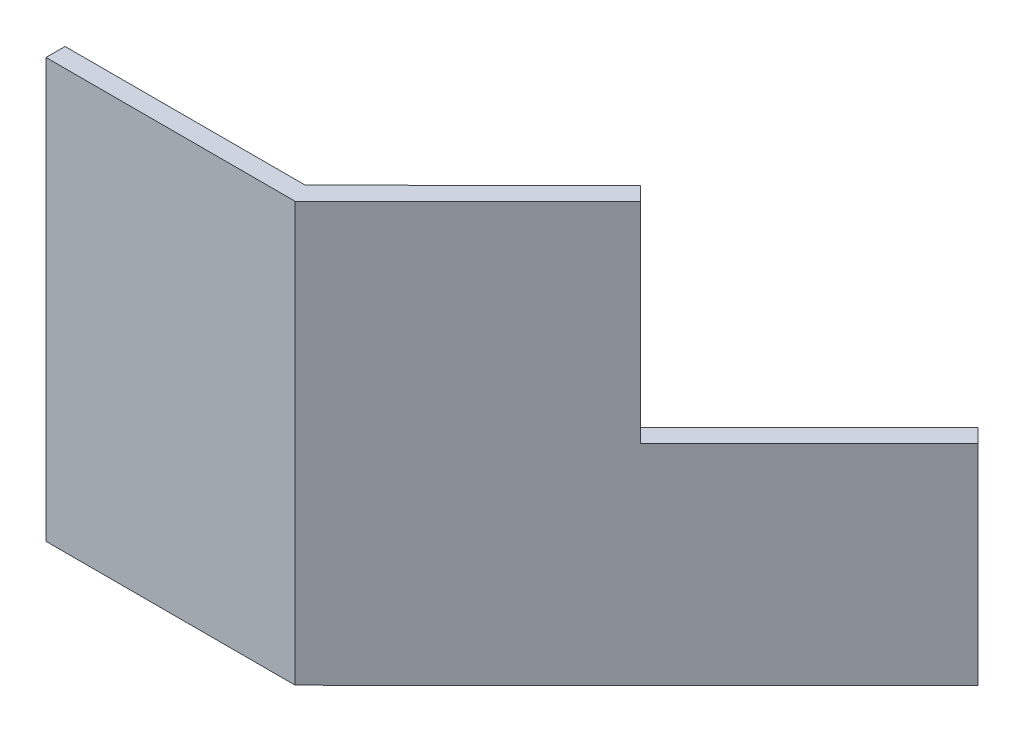
SolidWorks part; units mm, degrees
ref_plane "Front Plane" through (0, 0, 0) normal (0, 0, 1) x (1, 0, 0)
ref_plane "Top Plane" through (0, 0, 0) normal (0, 1, 0) x (1, 0, 0)
ref_plane "Right Plane" through (0, 0, 0) normal (1, 0, 0) x (0, 0, -1)
sketch "Sketch1" plane through (0, 0, 0) normal (0, 1, 0) x (1, 0, 0)
  line L1 (-0.2536, 0) -> (-4.6234, 0)
  line L3 (-0.0925, -0.3464) -> (-4.6234, -0.3464)
  line L4 (-4.6234, 0) -> (-4.6234, -0.3464)
  line L5 (-0.0925, -0.3464) -> (6.1198, 5.8559)
  line L6 (-0.2536, 0) -> (5.8662, 6.1099)
  line L7 (6.1198, 5.8559) -> (5.8662, 6.1099)
  line L8 (14.3962, 14.6261) -> (14.6497, 14.3721)
  point P0 (-23.2664, -0.7474)
extrude "Boss-Extrude1" add sketch "Sketch1" along normal blind 7.62 contours L1 L4 L3 L5 L7 L6
sketch "Sketch3" plane through (0, 7.62, 0) normal (0, 1, 0) x (1, 0, 0)
  line L0 (6.1198, 5.8559) -> (5.8662, 6.1099)
  line L1 (6.1198, 5.8559) -> (3.0474, 2.7884)
  line L2 (5.8662, 6.1099) -> (2.7938, 3.0424)
  line L3 (3.0474, 2.7884) -> (2.7938, 3.0424)
extrude "Cut-Extrude2" cut sketch "Sketch3" against normal blind 3.81
